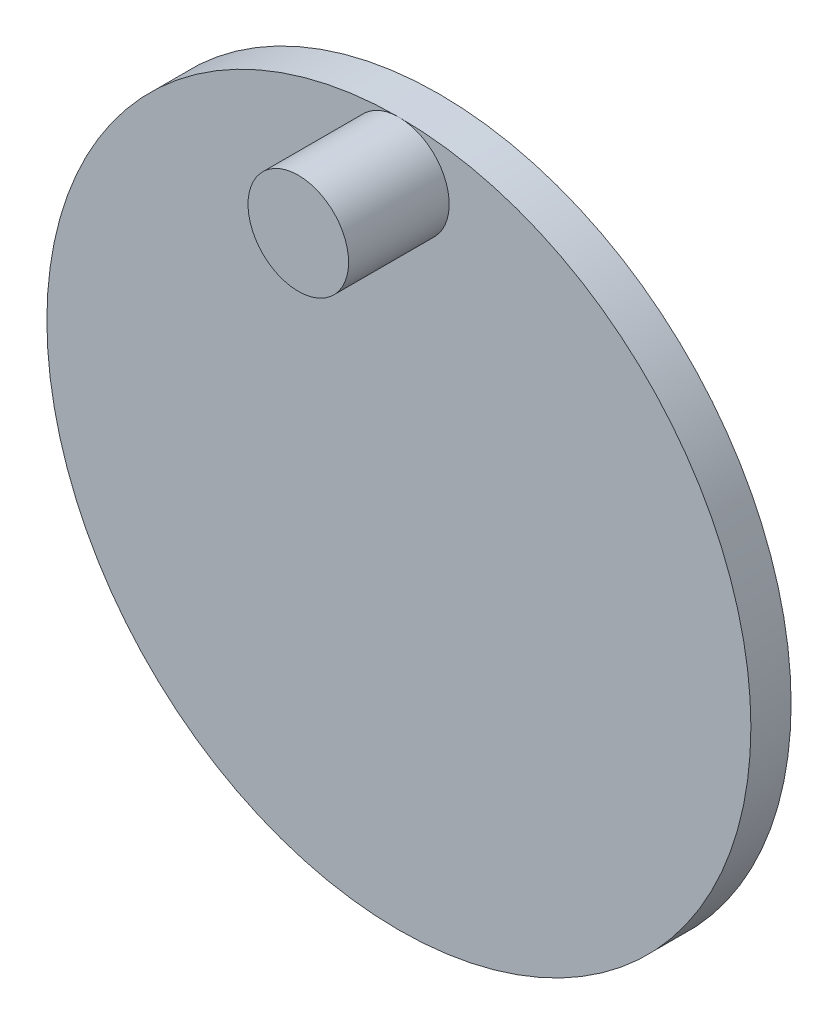
SolidWorks part; units mm, degrees
ref_plane "Front Plane" through (0, 0, 0) normal (0, 0, 1) x (1, 0, 0)
ref_plane "Top Plane" through (0, 0, 0) normal (0, 1, 0) x (1, 0, 0)
ref_plane "Right Plane" through (0, 0, 0) normal (1, 0, 0) x (0, 0, -1)
sketch "Sketch1" plane through (0, 0, 0) normal (0, 0, 1) x (1, 0, 0)
  circle A1 centre (0, 0) radius 17.5
  dimension "D2" = 35
extrude "Boss-Extrude1" add sketch "Sketch1" along normal blind 2
sketch "Sketch2" plane through (0, 0, 0) normal (0, 0, -1) x (-1, 0, 0)
  line L0 (-1.85, 1.9666) -> (1.85, 1.9666)
  line L1 (-1.85, -1.9666) -> (1.85, -1.9666)
  line L2 (0, 1.9666) -> (0, -1.9666) construction
  circle A0 centre (0, 0) radius 2.7
  circle A1 centre (0, 0) radius 3.7
  point P6 (0, 0)
  point P8 (0, 1.9666)
  point P14 (0, -1.9666)
  dimension "D2" = 5.4
  dimension "D3" = 7.4
  dimension "D1" = 3.7
extrude "Boss-Extrude3" add sketch "Sketch2" along normal blind 8 contours A1 A0 | L0 A0 | L1 A0 region at (0, 2.2637, 0) region at (0, -2.2637, 0) region at (3.5953, 0, 0)
sketch "Sketch4" plane through (0, 0, 2) normal (0, 0, 1) x (1, 0, 0)
  circle A0 centre (0, 15) radius 2.5
  dimension "D1" = 5
  dimension "D2" = 15
extrude "Boss-Extrude4" add sketch "Sketch4" along normal blind 5
